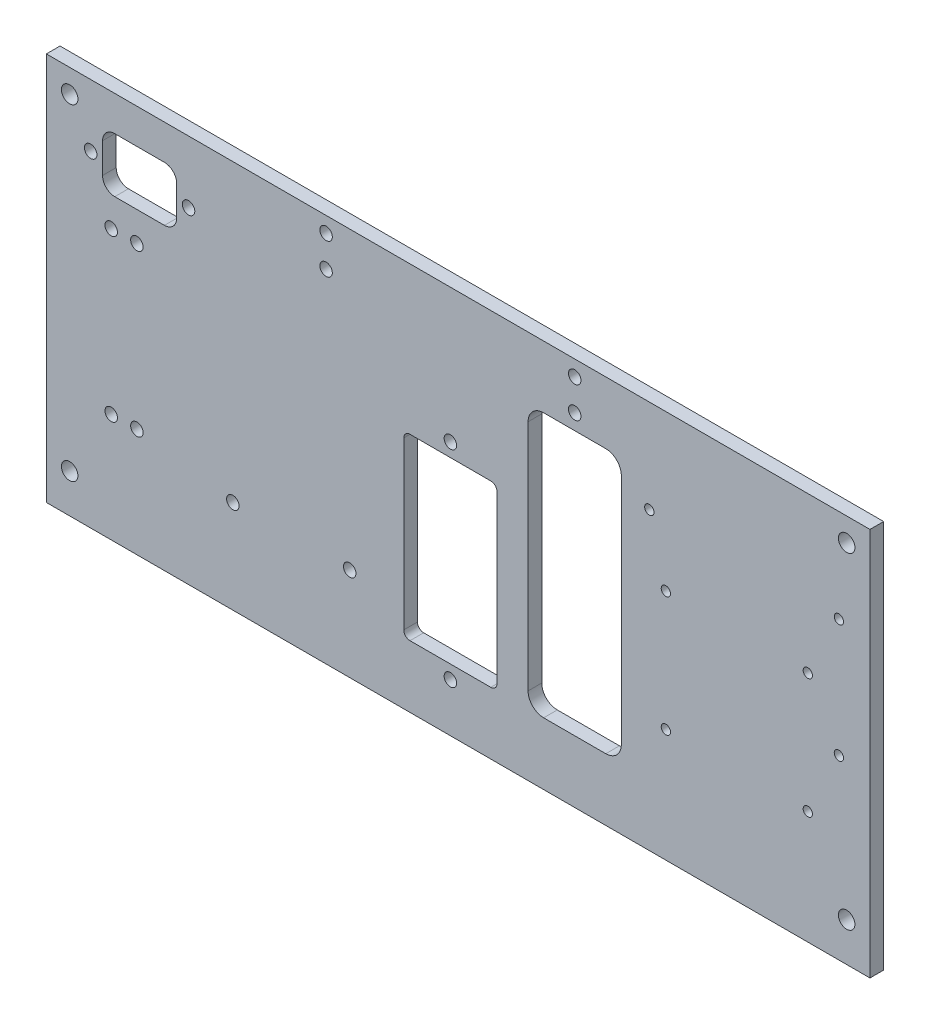
SolidWorks part; units mm, degrees
material "Acrylic (Medium-high impact)"
ref_plane "Front Plane" through (0, 0, 0) normal (0, 0, 1) x (1, 0, 0)
ref_plane "Top Plane" through (0, 0, 0) normal (0, 1, 0) x (1, 0, 0)
ref_plane "Right Plane" through (0, 0, 0) normal (1, 0, 0) x (0, 0, -1)
sketch "Sketch1" plane through (0, 0, 0) normal (0, 0, 1) x (1, 0, 0)
  line L1 (-168.275, 79.375) -> (168.275, 79.375)
  line L2 (-168.275, 79.375) -> (-168.275, -79.375)
  line L3 (-168.275, -79.375) -> (168.275, -79.375)
  line L4 (168.275, 79.375) -> (168.275, -79.375)
  line L5 (-168.275, 79.375) -> (168.275, -79.375) construction
  line L6 (-168.275, -79.375) -> (168.275, 79.375) construction
  point P0 (0, 0)
  dimension "D1" = 158.75
  dimension "D2" = 336.55
extrude "Boss-Extrude1" add sketch "Sketch1" along normal blind 5.588 contours L1 L4 L3 L2
hole_wizard "1/4 Clearance Hole1" positions "Sketch3" profile "Sketch2" hole size "1/4" standard "ANSI Inch" end condition up to next
sketch "Sketch3" plane through (0, 0, 0) normal (0, 0, -1) x (-1, 0, 0)
  line L1 (-158.75, 69.85) -> (158.75, 69.85) construction
  line L2 (-158.75, 69.85) -> (-158.75, -63.5) construction
  line L3 (-158.75, -63.5) -> (158.75, -63.5) construction
  line L4 (158.75, 69.85) -> (158.75, -63.5) construction
  line L5 (168.275, 79.375) -> (-168.275, 79.375) construction
  line L6 (-168.275, 79.375) -> (-168.275, -79.375) construction
  line L10 (168.275, 79.375) -> (168.275, -79.375) construction
  line L11 (168.275, -79.375) -> (-168.275, -79.375) construction
  point P1 (-158.75, 69.85)
  point P2 (158.75, -63.5)
  point P283 (-158.75, -63.5)
  point P284 (158.75, 69.85)
  dimension "D1" = 9.525
  dimension "D2" = 9.525
  dimension "D3" = 9.525
  dimension "D4" = 15.875
sketch "Sketch2" plane through (158.75, 69.85, 0) normal (1, 0, 0) x (0, 1, 0)
  line L0 (0, 0) -> (0, 5.588)
  line L1 (0, 5.588) -> (3.3782, 5.588)
  line L2 (3.3782, 5.588) -> (3.3782, 0)
  line L5 (3.3782, 0) -> (0, 0)
  line L11 (0, -6.35) -> (0, 107.95) construction
  dimension "Thru Hole Dia." = 6.7564
  dimension "Thru Hole Depth" = 5.588
hole_wizard "#6 Clearance Hole1" positions "Sketch6" profile "Sketch7" hole size "#6" standard "ANSI Inch" end condition up to next
sketch "Sketch6" plane through (0, 0, 0) normal (0, 0, -1) x (-1, 0, 0)
  line L1 (-155.575, 41.275) -> (-78.105, 41.275) construction
  line L2 (-155.575, 41.275) -> (-155.575, -6.985) construction
  line L3 (-155.575, -6.985) -> (-78.105, -6.985) construction
  line L4 (-78.105, 41.275) -> (-78.105, -6.985) construction
  line L5 (-168.275, 79.375) -> (-168.275, -79.375) construction
  line L6 (168.275, 79.375) -> (-168.275, 79.375) construction
  point P0 (-155.575, 41.275)
  point P105 (-155.575, -6.985)
  point P106 (-78.105, 41.275)
  dimension "D1" = 77.47
  dimension "D2" = 48.26
  dimension "D3" = 12.7
  dimension "D4" = 38.1
sketch "Sketch7" plane through (155.575, 41.275, 0) normal (1, 0, 0) x (0, 1, 0)
  line L0 (0, 0) -> (0, 5.588)
  line L1 (0, 5.588) -> (1.8986, 5.588)
  line L2 (1.8986, 5.588) -> (1.8986, 0)
  line L5 (1.8986, 0) -> (0, 0)
  line L11 (0, -6.35) -> (0, 107.95) construction
  dimension "Thru Hole Dia." = 3.7973
  dimension "Thru Hole Depth" = 5.588
hole_wizard "#6 Clearance Hole2" positions "Sketch9" profile "Sketch10" hole size "#6" standard "ANSI Inch" end condition up to next
sketch "Sketch9" plane through (0, 0, 0) normal (0, 0, -1) x (-1, 0, 0)
  line L1 (-142.875, 15.875) -> (-84.875, 15.875) construction
  line L2 (-142.875, 15.875) -> (-142.875, -33.125) construction
  line L3 (-142.875, -33.125) -> (-84.875, -33.125) construction
  line L4 (-84.875, 15.875) -> (-84.875, -33.125) construction
  line L5 (-168.275, 79.375) -> (-168.275, -79.375) construction
  line L6 (168.275, 79.375) -> (-168.275, 79.375) construction
  point P0 (-142.875, 15.875)
  point P1 (-84.875, -33.125)
  point P148 (-142.875, -33.125)
  point P149 (-84.875, 15.875)
  dimension "D1" = 58
  dimension "D2" = 49
  dimension "D3" = 25.4
  dimension "D4" = 63.5
sketch "Sketch10" plane through (142.875, 15.875, 0) normal (1, 0, 0) x (0, 1, 0)
  line L0 (0, 0) -> (0, 5.588)
  line L1 (0, 5.588) -> (1.8986, 5.588)
  line L2 (1.8986, 5.588) -> (1.8986, 0)
  line L5 (1.8986, 0) -> (0, 0)
  line L11 (0, -6.35) -> (0, 107.95) construction
  dimension "Thru Hole Dia." = 3.7973
  dimension "Thru Hole Depth" = 5.588
sketch "Sketch11" plane through (0, 0, 0) normal (0, 0, -1) x (-1, 0, 0)
  line L0 (168.275, 79.375) -> (168.275, -79.375) construction
  line L1 (-13.335, 19.05) -> (19.685, 19.05)
  line L2 (-15.875, 16.51) -> (-15.875, -51.435)
  line L3 (-13.335, -53.975) -> (19.685, -53.975)
  line L4 (22.225, 16.51) -> (22.225, -51.435)
  line L5 (168.275, -79.375) -> (-168.275, -79.375) construction
  arc A0 (19.685, 19.05) -> (22.225, 16.51) centre (19.685, 16.51) cw
  arc A1 (19.685, -53.975) -> (22.225, -51.435) centre (19.685, -51.435) ccw
  arc A2 (-15.875, -51.435) -> (-13.335, -53.975) centre (-13.335, -51.435) ccw
  arc A3 (-13.335, 19.05) -> (-15.875, 16.51) centre (-13.335, 16.51) ccw
  point P10 (22.225, 19.05)
  point P15 (-15.875, -53.975)
  point P18 (-15.875, 19.05)
  dimension "D5" = 2.54
  dimension "D1" = 38.1
  dimension "D2" = 73.025
  dimension "D3" = 146.05
  dimension "D4" = 25.4
extrude "Cut-Extrude1" cut sketch "Sketch11" against normal up to next
hole_wizard "#10 Clearance Hole1" positions "Sketch13" profile "Sketch14" hole size "#10" standard "ANSI Inch" end condition up to next
sketch "Sketch13" plane through (0, 0, 0) normal (0, 0, -1) x (-1, 0, 0)
  line L7 (-15.875, -17.4625) -> (3.175, -17.4625) construction
  line L8 (-15.875, 16.51) -> (-15.875, -51.435) construction
  line L10 (3.175, 24.6062) -> (3.175, -59.5313) construction
  point P12 (3.175, 24.6062)
  point P17 (3.175, -59.5313)
  dimension "D1" = 19.05
  dimension "D2" = 84.1375
sketch "Sketch14" plane through (-3.175, 24.6062, 0) normal (1, 0, 0) x (0, 1, 0)
  line L0 (0, 0) -> (0, 5.588)
  line L1 (0, 5.588) -> (2.5527, 5.588)
  line L2 (2.5527, 5.588) -> (2.5527, 0)
  line L5 (2.5527, 0) -> (0, 0)
  line L11 (0, -6.35) -> (0, 107.95) construction
  dimension "Thru Hole Dia." = 5.1054
  dimension "Thru Hole Depth" = 5.588
sketch "Sketch15" plane through (0, 0, 0) normal (0, 0, -1) x (-1, 0, 0)
  line L0 (-168.275, 79.375) -> (-168.275, -79.375) construction
  line L1 (-60.325, 53.975) -> (-34.925, 53.975)
  line L2 (-66.675, 47.625) -> (-66.675, -47.625)
  line L3 (-60.325, -53.975) -> (-34.925, -53.975)
  line L4 (-28.575, 47.625) -> (-28.575, -47.625)
  line L5 (168.275, 79.375) -> (-168.275, 79.375) construction
  line L6 (168.275, -79.375) -> (-168.275, -79.375) construction
  arc A0 (-34.925, 53.975) -> (-28.575, 47.625) centre (-34.925, 47.625) cw
  arc A1 (-34.925, -53.975) -> (-28.575, -47.625) centre (-34.925, -47.625) ccw
  arc A2 (-66.675, -47.625) -> (-60.325, -53.975) centre (-60.325, -47.625) ccw
  arc A3 (-60.325, 53.975) -> (-66.675, 47.625) centre (-60.325, 47.625) ccw
  point P12 (-28.575, 53.975)
  point P19 (-66.675, 53.975)
  dimension "D5" = 6.35
  dimension "D1" = 101.6
  dimension "D2" = 25.4
  dimension "D3" = 25.4
  dimension "D4" = 38.1
extrude "Cut-Extrude2" cut sketch "Sketch15" against normal up to next
hole_wizard "#10 Clearance Hole3" positions "Sketch17" profile "Sketch18" hole size "#10" standard "ANSI Inch" end condition up to next
sketch "Sketch17" plane through (0, 0, 0) normal (0, 0, -1) x (-1, 0, 0)
  line L4 (131.2799, 30.7848) -> (141.7701, 30.7848) construction
  line L7 (131.2799, -34.925) -> (141.7701, -34.925) construction
  line L9 (136.525, 30.7848) -> (136.525, -34.925) construction
  line L10 (168.275, 79.375) -> (168.275, -79.375) construction
  line L11 (168.275, -79.375) -> (-168.275, -79.375) construction
  point P0 (131.2799, 30.7848)
  point P1 (131.2799, -34.925)
  point P17 (141.7701, 30.7848)
  point P23 (141.7701, -34.925)
  dimension "D1" = 10.4902
  dimension "D2" = 65.7098
  dimension "D3" = 31.75
  dimension "D4" = 44.45
sketch "Sketch18" plane through (-131.2799, 30.7848, 0) normal (1, 0, 0) x (0, 1, 0)
  line L0 (0, 0) -> (0, 5.588)
  line L1 (0, 5.588) -> (2.5527, 5.588)
  line L2 (2.5527, 5.588) -> (2.5527, 0)
  line L5 (2.5527, 0) -> (0, 0)
  line L11 (0, -6.35) -> (0, 107.95) construction
  dimension "Thru Hole Dia." = 5.1054
  dimension "Thru Hole Depth" = 5.588
hole_wizard "#10 Clearance Hole2" positions "Sketch20" profile "Sketch21" hole size "#10" standard "ANSI Inch" end condition up to next
sketch "Sketch20" plane through (0, 0, 0) normal (0, 0, -1) x (-1, 0, 0)
  line L2 (-47.625, 73.025) -> (53.975, 73.025) construction
  line L3 (-47.625, 73.025) -> (-47.625, 60.325) construction
  line L4 (-47.625, 60.325) -> (53.975, 60.325) construction
  line L5 (53.975, 73.025) -> (53.975, 60.325) construction
  line L6 (168.275, 79.375) -> (168.275, -79.375) construction
  line L7 (168.275, 79.375) -> (-168.275, 79.375) construction
  point P3 (-47.625, 73.025)
  point P4 (53.975, 60.325)
  point P287 (-47.625, 60.325)
  point P288 (53.975, 73.025)
  dimension "D1" = 101.6
  dimension "D2" = 12.7
  dimension "D3" = 114.3
  dimension "D4" = 6.35
sketch "Sketch21" plane through (47.625, 73.025, 0) normal (1, 0, 0) x (0, 1, 0)
  line L0 (0, 0) -> (0, 5.588)
  line L1 (0, 5.588) -> (2.5527, 5.588)
  line L2 (2.5527, 5.588) -> (2.5527, 0)
  line L5 (2.5527, 0) -> (0, 0)
  line L11 (0, -6.35) -> (0, 107.95) construction
  dimension "Thru Hole Dia." = 5.1054
  dimension "Thru Hole Depth" = 5.588
hole_wizard "#10 Clearance Hole4" positions "Sketch23" profile "Sketch22" hole size "#10" standard "ANSI Inch" end condition up to next
sketch "Sketch23" plane through (0, 0, 0) normal (0, 0, -1) x (-1, 0, 0)
  line L0 (44.323, -41.275) -> (92.075, -41.275) construction
  line L6 (168.275, -79.375) -> (-168.275, -79.375) construction
  line L7 (168.275, 79.375) -> (168.275, -79.375) construction
  point P1 (44.323, -41.275)
  point P2 (92.075, -41.275)
  dimension "D1" = 47.752
  dimension "D2" = 38.1
  dimension "D3" = 76.2
sketch "Sketch22" plane through (-44.323, -41.275, 0) normal (1, 0, 0) x (0, 1, 0)
  line L0 (0, 0) -> (0, 5.588)
  line L1 (0, 5.588) -> (2.5527, 5.588)
  line L2 (2.5527, 5.588) -> (2.5527, 0)
  line L5 (2.5527, 0) -> (0, 0)
  line L11 (0, -6.35) -> (0, 107.95) construction
  dimension "Thru Hole Dia." = 5.1054
  dimension "Thru Hole Depth" = 5.588
sketch "Sketch24" plane through (0, 0, 0) normal (0, 0, -1) x (-1, 0, 0)
  line L0 (130.175, 65.125) -> (130.175, 42.825) construction
  line L1 (120.025, 65.125) -> (140.325, 65.125)
  line L2 (115.025, 60.125) -> (115.025, 47.825)
  line L3 (120.025, 42.825) -> (140.325, 42.825)
  line L4 (145.325, 60.125) -> (145.325, 47.825)
  line L5 (150.175, 53.975) -> (110.175, 53.975) construction
  line L6 (168.275, 79.375) -> (-168.275, 79.375) construction
  line L7 (168.275, 79.375) -> (168.275, -79.375) construction
  circle A0 centre (110.175, 53.975) radius 2.5527
  circle A1 centre (150.175, 53.975) radius 2.5527
  arc A2 (140.325, 65.125) -> (145.325, 60.125) centre (140.325, 60.125) cw
  arc A3 (140.325, 42.825) -> (145.325, 47.825) centre (140.325, 47.825) ccw
  arc A4 (115.025, 47.825) -> (120.025, 42.825) centre (120.025, 47.825) ccw
  arc A5 (120.025, 65.125) -> (115.025, 60.125) centre (120.025, 60.125) ccw
  point P9 (130.175, 53.975)
  point P13 (145.325, 65.125)
  point P16 (145.325, 42.825)
  point P21 (115.025, 65.125)
  dimension "D4" = 5.1054
  dimension "D5" = 5
  dimension "D1" = 30.3
  dimension "D2" = 22.3
  dimension "D3" = 40
  dimension "D6" = 25.4
  dimension "D7" = 38.1
extrude "Cut-Extrude3" cut sketch "Sketch24" against normal up to next
